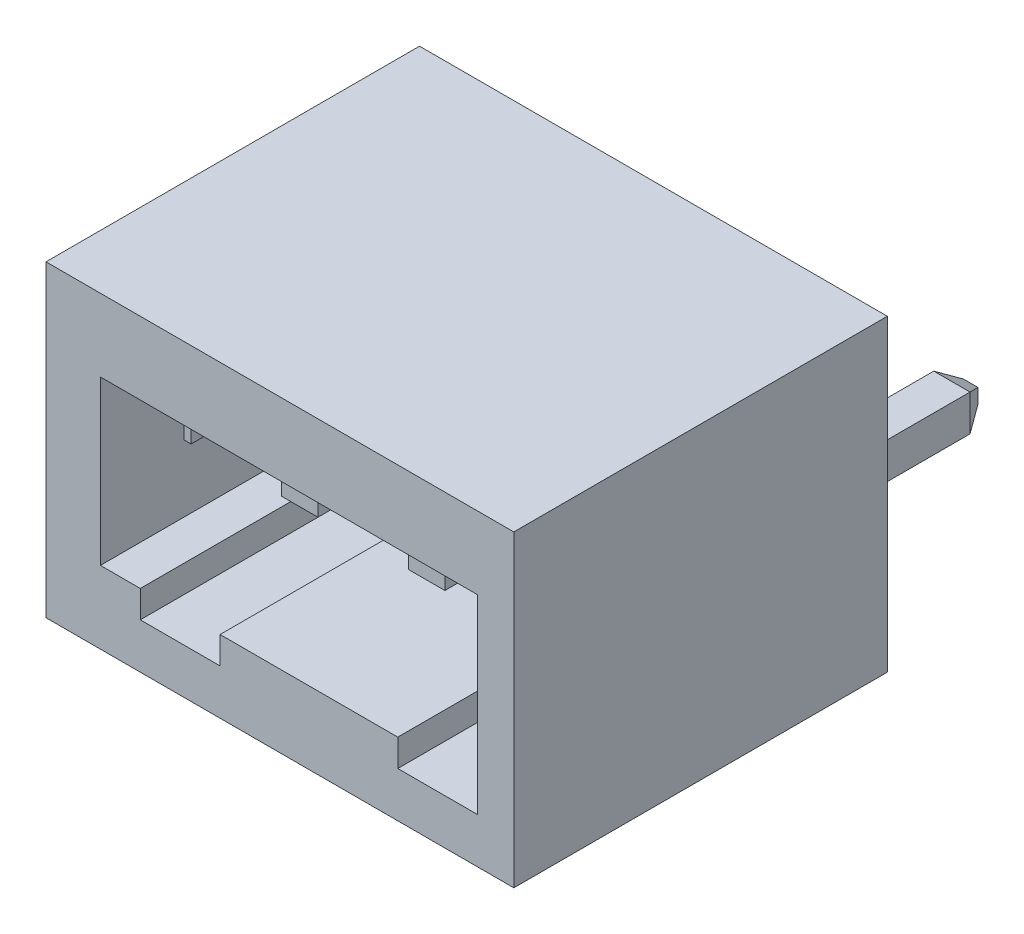
SolidWorks part; units mm, degrees
other "Детальный элемент1"
ref_plane "Спереди" through (0, 0, 0) normal (0, 0, 1) x (1, 0, 0)
ref_plane "Сверху" through (0, 0, 0) normal (0, 1, 0) x (1, 0, 0)
ref_plane "Справа" through (0, 0, 0) normal (1, 0, 0) x (0, 0, -1)
ref_axis "Ось1" through (80.9, 0, 0) along (-1, 0, 0)
sketch "Эскиз1" plane through (0, 0, 0) normal (0, 0, 1) x (1, 0, 0)
  line L0 (50, 0) -> (-50, 0) construction
  line L1 (-5.75, -0.5) -> (-4.75, -0.5)
  line L2 (-5.75, -0.5) -> (-5.75, 0.5)
  line L3 (-5.75, 0.5) -> (-4.75, 0.5)
  line L4 (-4.75, -0.5) -> (-4.75, 0.5)
  line L5 (-5.75, -0.5) -> (-4.75, 0.5) construction
  line L6 (-5.75, 0.5) -> (-4.75, -0.5) construction
  point P0 (-5.25, 0)
  dimension "D1" = 5.25
  dimension "D2" = 1
  dimension "D3" = 1
extrude "Бобышка-Вытянуть1" add sketch "Эскиз1" along normal blind 8 and the other way blind 3.5
chamfer "Фаска1" distance 0.3 angle 60 4 edges at (-5.25, -0.5, -3.5) (-5.75, 0, -3.5) (-5.25, 0.5, -3.5) (-4.75, 0, -3.5) first distance on face at (-5.25, 0, -3.5)
pattern_linear "Линейный массив1" count 4 spacing 3.5 along (1, 0, 0) of bodies 107
sketch "Эскиз3" plane through (0, 0, 0) normal (0, 0, 1) x (1, 0, 0)
  line L0 (0, -50) -> (0, 50) construction
  line L1 (6.45, 4.15) -> (-6.45, 4.15)
  line L2 (6.45, 4.15) -> (6.45, -4.35)
  line L3 (6.45, -4.35) -> (-6.45, -4.35)
  line L4 (-6.45, 4.15) -> (-6.45, -4.35)
  line L5 (6.45, 4.15) -> (-6.45, -4.35) construction
  line L6 (6.45, -4.35) -> (-6.45, 4.15) construction
  point P0 (0, -0.1)
  dimension "D1" = 8.5
  dimension "D2" = 12.9
  dimension "D3" = 4.35
extrude "Бобышка-Вытянуть2" add sketch "Эскиз3" along normal blind 10.3 separate body
shell "Оболочка1" thickness 2 removed face at (0, -0.1, 10.3)
sketch "Эскиз4" plane through (0, 0, 10.3) normal (0, 0, 1) x (1, 0, 0)
  line L0 (-4.95, -2.35) -> (5.45, -2.35) construction
  line L1 (-3.85, -2.35) -> (-1.65, -2.35)
  line L2 (-3.85, -2.35) -> (-3.85, -3.1)
  line L3 (-3.85, -3.1) -> (-1.65, -3.1)
  line L4 (-1.65, -2.35) -> (-1.65, -3.1)
  line L5 (-6.45, 4.15) -> (-6.45, -4.35) construction
  line L6 (3.25, -2.35) -> (5.45, -2.35)
  line L7 (3.25, -2.35) -> (3.25, -3.1)
  line L8 (3.25, -3.1) -> (5.45, -3.1)
  line L9 (5.45, -2.35) -> (5.45, -3.1)
  line L10 (6.45, -4.35) -> (6.45, 4.15) construction
  dimension "D1" = 2.2
  dimension "D2" = 0.75
  dimension "D3" = 4.8
  dimension "D4" = 3.2
extrude "Вырез-Вытянуть1" cut sketch "Эскиз4" against normal up to surface (8.8 mm away) up to face at (0.25, -0.1, 1.5)
